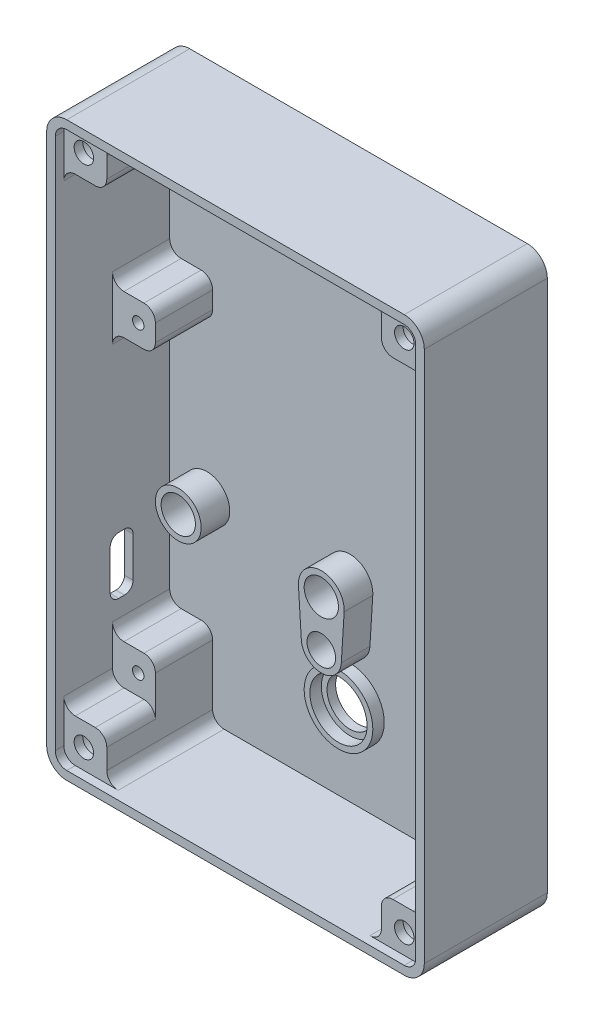
SolidWorks part; units mm, degrees
material "ABS"
ref_plane "Спереди" through (0, 0, 0) normal (0, 0, 1) x (1, 0, 0)
ref_plane "Сверху" through (0, 0, 0) normal (0, 1, 0) x (1, 0, 0)
ref_plane "Справа" through (0, 0, 0) normal (1, 0, 0) x (0, 0, -1)
sketch "Эскиз1" plane through (0, 0, 0) normal (0, 0, 1) x (1, 0, 0)
  line L1 (-33, -50) -> (33, -50)
  line L2 (-33, -50) -> (-33, 50)
  line L3 (-33, 50) -> (33, 50)
  line L4 (33, -50) -> (33, 50)
  line L5 (-33, -50) -> (33, 50) construction
  line L6 (-33, 50) -> (33, -50) construction
  line L7 (-31.5, -48.5) -> (31.5, -48.5)
  line L8 (-31.5, -48.5) -> (-31.5, 48.5)
  line L9 (-31.5, 48.5) -> (31.5, 48.5)
  line L10 (31.5, -48.5) -> (31.5, 48.5)
  line L11 (-31.5, -48.5) -> (31.5, 48.5) construction
  line L12 (-31.5, 48.5) -> (31.5, -48.5) construction
  point P0 (0, 0)
  point P6 (0, 0)
  dimension "D1" = 66
  dimension "D2" = 100
  dimension "D3" = 1.5
  dimension "D4" = 1.5
extrude "Бобышка-Вытянуть1" add sketch "Эскиз1" along normal blind 20
sketch "Эскиз3" plane through (0, 0, 0) normal (0, 0, -1) x (-1, 0, 0)
  line L1 (-33, 50) -> (33, 50)
  line L2 (-33, 50) -> (-33, -50)
  line L3 (-33, -50) -> (33, -50)
  line L4 (33, 50) -> (33, -50)
extrude "Бобышка-Вытянуть2" add sketch "Эскиз3" along normal blind 1.5
sketch "Эскиз4" plane through (0, 0, 0) normal (0, 0, 1) x (1, 0, 0)
  line L0 (-31.5, 48.5) -> (-31.5, -48.5) construction
  line L1 (-31.5, 19) -> (-24, 19)
  line L2 (-31.5, 19) -> (-31.5, 12)
  line L3 (-31.5, 12) -> (-24, 12)
  line L4 (-24, 19) -> (-24, 12)
  line L5 (31.5, -48.5) -> (31.5, 48.5) construction
  line L6 (31.5, 19) -> (24, 19)
  line L7 (31.5, 19) -> (31.5, 12)
  line L8 (31.5, 12) -> (24, 12)
  line L9 (24, 19) -> (24, 12)
  line L10 (-31.5, -48.5) -> (31.5, -48.5) construction
  line L11 (-31.5, -41) -> (-24, -41)
  line L12 (-31.5, -41) -> (-31.5, -34)
  line L13 (-31.5, -34) -> (-24, -34)
  line L14 (-24, -41) -> (-24, -34)
  line L15 (31.5, -41) -> (24, -41)
  line L16 (31.5, -41) -> (31.5, -34)
  line L17 (31.5, -34) -> (24, -34)
  line L18 (24, -41) -> (24, -34)
  line L19 (31.5, -48.5) -> (31.5, 48.5) construction
  dimension "D1" = 7.5
  dimension "D2" = 7
  dimension "D3" = 7
  dimension "D4" = 46
  dimension "D5" = 7.5
extrude "Бобышка-Вытянуть3" add sketch "Эскиз4" along normal blind 10
sketch "Эскиз5" plane through (0, 0, 10) normal (0, 0, 1) x (1, 0, 0)
  line L1 (-24, -41) -> (-24, -34) construction
  line L2 (-24, 12) -> (-24, 19) construction
  circle A0 centre (-27, 15.5) radius 1
  circle A1 centre (27, 15.5) radius 1
  circle A2 centre (-27, -37.5) radius 1
  circle A3 centre (27, -37.5) radius 1
  point P4 (0, 0)
  point P7 (0, 0)
  point P10 (-24, 15.5)
  point P11 (0, 0)
  point P13 (-27, -37.5)
  dimension "D5" = 2
  dimension "D6" = 53
  dimension "D1" = 54
  dimension "D2" = 3
sketch "Эскиз8" plane through (0, 0, 0) normal (0, 0, 1) x (1, 0, 0)
  line L0 (-24, -41) -> (-24, -34) construction
  line L1 (-31.5, 48.5) -> (-24, 48.5)
  line L2 (-31.5, 48.5) -> (-31.5, 41)
  line L3 (-31.5, 41) -> (-24, 41)
  line L4 (-24, 48.5) -> (-24, 41)
  line L5 (31.5, 48.5) -> (24, 48.5)
  line L6 (31.5, 48.5) -> (31.5, 41)
  line L7 (31.5, 41) -> (24, 41)
  line L8 (24, 48.5) -> (24, 41)
  line L9 (31.5, -48.5) -> (24, -48.5)
  line L10 (31.5, -48.5) -> (31.5, -41)
  line L11 (31.5, -41) -> (24, -41)
  line L12 (24, -48.5) -> (24, -41)
  line L13 (-31.5, -48.5) -> (-24, -48.5)
  line L14 (-31.5, -48.5) -> (-31.5, -41)
  line L15 (-31.5, -41) -> (-24, -41)
  line L16 (-24, -48.5) -> (-24, -41)
  line L18 (24, -34) -> (24, -41) construction
  line L19 (-24, 19) -> (-31.5, 19) construction
  line L21 (-31.5, -41) -> (-24, -41) construction
extrude "Бобышка-Вытянуть4" add sketch "Эскиз8" along normal blind 18.5
fillet "Скругление1" radius 2 20 edges at (-31.5, -34, 5) (-24, -34, 5) (-24, -48.5, 9.25) (24, -48.5, 9.25) (24, -34, 5) (31.5, -34, 5) (31.5, 12, 5) (24, 12, 5) (24, 19, 5) (31.5, 19, 5) (-31.5, 12, 5) (-24, 12, 5) (-24, 19, 5) (-31.5, 19, 5) (-31.5, 41, 9.25) (-24, 41, 9.25) (-24, 48.5, 9.25) (31.5, 41, 9.25) (24, 48.5, 9.25) (24, 41, 9.25)
fillet "Скругление3" radius 2 8 edges at (-31.5, -48.5, 19.25) (-31.5, -41, 14.25) (-24, -41, 14.25) (31.5, -48.5, 19.25) (24, -41, 14.25) (31.5, -41, 14.25) (-31.5, 48.5, 19.25) (31.5, 48.5, 19.25)
fillet "Скругление4" radius 3.5 4 edges at (-33, -50, 9.25) (33, -50, 9.25) (33, 50, 9.25) (-33, 50, 9.25)
sketch "Эскиз9" plane through (0, 0, 0) normal (0, 0, 1) x (1, 0, 0)
  circle A0 centre (-25, -15) radius 3
  circle A1 centre (25, -15) radius 3
  circle A2 centre (0, -23) radius 2.5
  circle A3 centre (0, -15) radius 3
  circle A4 centre (0, -33.5) radius 4
  dimension "D1" = 6
  dimension "D6" = 8
  dimension "D8" = 5
  dimension "D2" = 8
  dimension "D3" = 10.5
  dimension "D4" = 25
  dimension "D5" = 25
  dimension "D7" = 4
extrude "Вырез-Вытянуть1" cut sketch "Эскиз9" against normal through all
sketch "Эскиз10" plane through (0, 0, 0) normal (0, 0, 1) x (1, 0, 0)
  line L0 (3.9922, -15.25) -> (3.4932, -23.2188)
  line L1 (-3.9922, -15.25) -> (-3.4932, -23.2188)
  circle A0 centre (-25, -15) radius 3
  circle A1 centre (0, -23) radius 2.5 construction
  circle A2 centre (0, -15) radius 3
  circle A3 centre (25, -15) radius 3
  circle A4 centre (0, -23) radius 2.5
  circle A5 centre (-25, -15) radius 3 construction
  circle A6 centre (0, -15) radius 4
  circle A7 centre (25, -15) radius 4
  circle A9 centre (-25, -15) radius 4
  arc A12 (-3.4932, -23.2188) -> (3.4932, -23.2188) centre (0, -23) ccw
  circle M1 centre (-25, -15) radius 3
  circle M2 centre (0, -15) radius 3
  circle M3 centre (0, -23) radius 2.5
  circle M4 centre (25, -15) radius 3
  dimension "D1" = 1
  dimension "D2" = 1
extrude "Бобышка-Вытянуть5" add sketch "Эскиз10" along normal blind 5 contours L1 A12 L0 A6 M3 | A6 M2 | A7 M4 | A9 M1 region at (3.605, -19.2258, 0) region at (0, -18.8869, 0) region at (21.1131, -15, 0) region at (-28.8869, -15, 0)
sketch "Эскиз11" plane through (0, 0, -1.5) normal (0, 0, -1) x (-1, 0, 0)
  line L0 (29.5, 50) -> (-29.5, 50) construction
  line L1 (33, -46.5) -> (33, 46.5) construction
  line L2 (-29.5, -50) -> (29.5, -50) construction
  line L3 (-33, 46.5) -> (-33, -46.5) construction
  circle A0 centre (-28, 45) radius 3
  circle A1 centre (28, 45) radius 3
  circle A2 centre (28, -45) radius 3
  circle A3 centre (-28, -45) radius 3
  dimension "D2" = 6
  dimension "D1" = 5
  dimension "D3" = 5
  dimension "D4" = 5
  dimension "D5" = 5
extrude "Вырез-Вытянуть2" cut sketch "Эскиз11" against normal blind 18.5
sketch "Эскиз12" plane through (0, 0, 17) normal (0, 0, -1) x (-1, 0, 0)
  point P0 (-28, 45)
  point P1 (28, 45)
  point P3 (28, -45)
  point P5 (-28, -45)
hole_wizard "Отверстие с зазором M31" positions "Эскиз13" profile "Эскиз14" hole size "M3" standard "DIN" end condition through all
sketch "Эскиз13" plane through (0, 0, 17) normal (0, 0, -1) x (-1, 0, 0)
  point P0 (-28, 45)
  point P3 (28, 45)
  point P6 (28, -45)
  point P9 (-28, -45)
sketch "Эскиз14" plane through (28, 45, 17) normal (1, 0, 0) x (0, 1, 0)
  line L0 (0, 0) -> (0, 3)
  line L1 (0, 3) -> (1.7, 3)
  line L2 (1.7, 3) -> (1.7, 0)
  line L5 (1.7, 0) -> (0, 0)
  line L11 (0, -6.35) -> (0, 107.95) construction
  dimension "Диаметр сквозного отверстия" = 3.4
  dimension "Глубина сквозного отверстия" = 3
extrude "Вырез-Вытянуть4" cut sketch "Эскиз5" against normal blind 4
sketch "Эскиз15" plane through (-31.5, 0, 0) normal (-1, 0, 0) x (0, 0, 1)
  line L1 (6.4, -29) -> (10.4, -29)
  line L2 (6.4, -29) -> (6.4, -19)
  line L3 (6.4, -19) -> (10.4, -19)
  line L4 (10.4, -29) -> (10.4, -19)
  line L5 (10, -39) -> (10, -32) construction
  dimension "D1" = 4
  dimension "D2" = 10
  dimension "D3" = 8.5
  dimension "D4" = 0.4
extrude "Вырез-Вытянуть3" cut sketch "Эскиз15" along normal up to surface (1.5 mm away) up to face at (-33, 0, 9.25)
fillet "Скругление5" radius 1.5 4 edges at (-32.25, -29, 10.4) (-32.25, -19, 10.4) (-32.25, -19, 6.4) (-32.25, -29, 6.4)
sketch "Эскиз16" plane through (0, 0, 0) normal (0, 0, 1) x (1, 0, 0)
  circle A0 centre (0, -33.5) radius 5
  circle A1 centre (0, -33.5) radius 6
  dimension "D1" = 1
  dimension "D2" = 10
extrude "Бобышка-Вытянуть6" add sketch "Эскиз16" along normal blind 2
